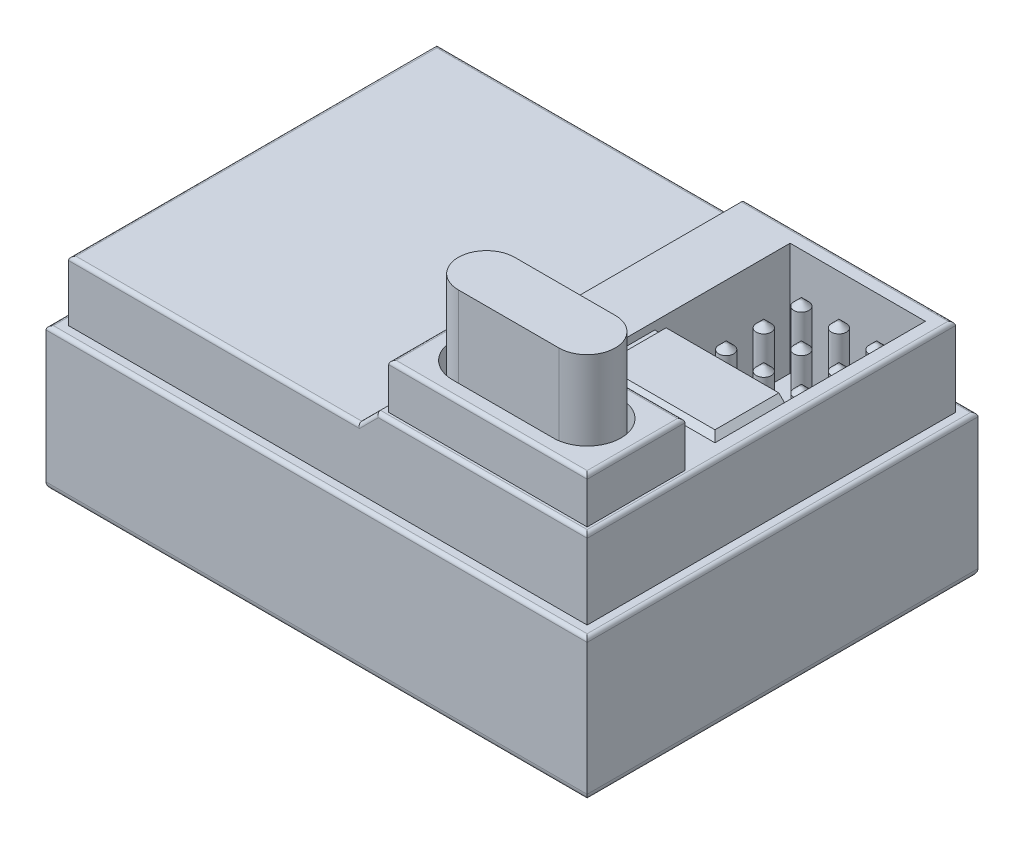
SolidWorks part; units mm, degrees
material "ABS"
ref_plane "Front Plane" through (0, 0, 0) normal (0, 0, 1) x (1, 0, 0)
ref_plane "Top Plane" through (0, 0, 0) normal (0, 1, 0) x (1, 0, 0)
ref_plane "Right Plane" through (0, 0, 0) normal (1, 0, 0) x (0, 0, -1)
sketch "Sketch1" plane through (0, 0, 0) normal (0, 1, 0) x (1, 0, 0)
  line L1 (-18, -13) -> (18, -13)
  line L2 (-18, -13) -> (-18, 13)
  line L3 (-18, 13) -> (18, 13)
  line L4 (18, -13) -> (18, 13)
  line L5 (-18, -13) -> (18, 13) construction
  line L6 (-18, 13) -> (18, -13) construction
  point P0 (0, 0)
  dimension "D1" = 26
  dimension "D2" = 36
extrude "Boss-Extrude1" add sketch "Sketch1" along normal blind 9.5
sketch "Sketch2" plane through (0, 9.5, 0) normal (0, 1, 0) x (1, 0, 0)
  line L0 (-18, 13) -> (-18, -13) construction
  line L1 (-17.25, -12.25) -> (17.25, -12.25)
  line L2 (-17.25, -12.25) -> (-17.25, 12.25)
  line L3 (-17.25, 12.25) -> (17.25, 12.25)
  line L4 (17.25, -12.25) -> (17.25, 12.25)
  line L5 (-17.25, -12.25) -> (17.25, 12.25) construction
  line L6 (-17.25, 12.25) -> (17.25, -12.25) construction
  line L7 (-18, -13) -> (18, -13) construction
  point P0 (0, 0)
  dimension "D1" = 0.75
  dimension "D2" = 0.75
extrude "Boss-Extrude2" add sketch "Sketch2" along normal blind 4
sketch "Sketch3" plane through (0, 13.5, 0) normal (0, 1, 0) x (1, 0, 0)
  line L0 (17.25, 12.25) -> (-17.25, 12.25) construction
  line L1 (17.25, -12.25) -> (2, -12.25)
  line L2 (17.25, -12.25) -> (17.25, 12.25)
  line L3 (17.25, 12.25) -> (2, 12.25)
  line L4 (2, -12.25) -> (2, 12.25)
  dimension "D1" = 15.25
extrude "Boss-Extrude3" add sketch "Sketch3" along normal blind 1.25
chamfer "Chamfer1" distance 1.25 angle 45 1 edges at (2, 14.75, 0)
sketch "Sketch4" plane through (0, 14.75, 0) normal (0, 1, 0) x (1, 0, 0)
  line L0 (3.25, -12.25) -> (17.25, -12.25) construction
  line L1 (16.85, -11.85) -> (3.65, -11.85)
  line L2 (16.85, -11.85) -> (16.85, -5.35)
  line L3 (16.85, -5.35) -> (3.65, -5.35)
  line L4 (3.65, -11.85) -> (3.65, -5.35)
  line L5 (17.25, -12.25) -> (17.25, 12.25) construction
  line L6 (3.25, 12.25) -> (3.25, -12.25) construction
  line L7 (6.9, -6.35) -> (13.6, -6.35)
  line L8 (13.6, -10.85) -> (6.9, -10.85)
  arc A0 (13.6, -6.35) -> (13.6, -10.85) centre (13.6, -8.6) cw
  arc A1 (6.9, -10.85) -> (6.9, -6.35) centre (6.9, -8.6) cw
  dimension "D7" = 1
  dimension "D8" = 1
  dimension "D1" = 0.4
  dimension "D2" = 0.4
  dimension "D3" = 0.4
  dimension "D4" = 6.5
  dimension "D5" = 1
  dimension "D6" = 1
extrude "Boss-Extrude4" add sketch "Sketch4" along normal blind 3
sketch "Sketch5" plane through (0, 14.75, 0) normal (0, 1, 0) x (1, 0, 0)
  line L0 (6.905, -6.725) -> (13.595, -6.725)
  line L1 (13.595, -10.475) -> (6.905, -10.475)
  line L2 (13.595, -8.6) -> (6.905, -8.6) construction
  line L3 (13.6, -6.35) -> (6.9, -6.35) construction
  line L4 (6.9, -10.85) -> (13.6, -10.85) construction
  line L5 (10.25, -10.85) -> (10.25, -6.35) construction
  line L6 (6.9, -10.85) -> (13.6, -10.85) construction
  arc A0 (13.595, -6.725) -> (13.595, -10.475) centre (13.595, -8.6) cw
  arc A1 (6.905, -10.475) -> (6.905, -6.725) centre (6.905, -8.6) cw
  arc A2 (6.9, -6.35) -> (6.9, -10.85) centre (6.9, -8.6) ccw construction
  point P5 (10.25, -6.35)
  point P7 (10.25, -10.85)
  point P16 (10.25, -8.6)
  point P17 (4.65, -8.6)
  dimension "D2" = 0.38
  dimension "D1" = 3.75
extrude "Boss-Extrude5" add sketch "Sketch5" along normal blind 8
sketch "Sketch6" plane through (0, 14.75, 0) normal (0, 1, 0) x (1, 0, 0)
  line L0 (17.25, 12.25) -> (3.25, 12.25) construction
  line L1 (7.25, 11.25) -> (16.25, 11.25)
  line L2 (7.25, 11.25) -> (7.25, -2.75)
  line L3 (7.25, -2.75) -> (16.25, -2.75)
  line L4 (16.25, 11.25) -> (16.25, -2.75)
  line L5 (17.25, -12.25) -> (17.25, 12.25) construction
  dimension "D1" = 14
  dimension "D2" = 1
  dimension "D3" = 1
  dimension "D4" = 9
extrude "Cut-Extrude1" cut sketch "Sketch6" against normal blind 7.5
sketch "Sketch7" plane through (0, 7.25, 0) normal (0, 1, 0) x (1, 0, 0)
  line L0 (16.25, 10) -> (7.25, 10) construction
  line L1 (16.25, -2.75) -> (16.25, 11.25) construction
  line L2 (7.25, 11.25) -> (7.25, -2.75) construction
  line L3 (16.25, 7.5) -> (7.25, 7.5) construction
  line L4 (7.25, 11.25) -> (7.25, -2.75) construction
  line L5 (7.25, 5) -> (16.25, 5) construction
  line L6 (16.25, 11.25) -> (7.25, 11.25) construction
  line L7 (14.25, 5) -> (14.25, 10) construction
  line L8 (9.25, 10) -> (9.25, 5) construction
  circle A0 centre (9.25, 10) radius 0.5
  circle A1 centre (11.75, 10) radius 0.5
  circle A2 centre (14.25, 10) radius 0.5
  circle A3 centre (9.25, 7.5) radius 0.5
  circle A4 centre (11.75, 7.5) radius 0.5
  circle A5 centre (14.25, 7.5) radius 0.5
  circle A6 centre (9.25, 5) radius 0.5
  circle A7 centre (11.75, 5) radius 0.5
  circle A8 centre (14.25, 5) radius 0.5
  point P14 (11.75, 10)
  point P15 (11.75, 7.5)
  point P16 (11.75, 5)
  dimension "D6" = 1
  dimension "D1" = 1.25
  dimension "D2" = 2.5
  dimension "D3" = 2.5
  dimension "D4" = 2.5
  dimension "D5" = 2.5
extrude "Boss-Extrude6" add sketch "Sketch7" along normal blind 6
chamfer "Chamfer3" distance 0.5 angle 45 9 edges at (14.25, 13.25, -4.5) (11.75, 13.25, -9.5) (11.75, 13.25, -4.5) (9.25, 13.25, -4.5) (9.25, 13.25, -7) (11.75, 13.25, -7) (14.25, 13.25, -7) (14.25, 13.25, -9.5) (9.25, 13.25, -9.5)
sketch "Sketch8" plane through (0, 7.25, 0) normal (0, 1, 0) x (1, 0, 0)
  line L0 (7.25, 11.25) -> (7.25, -2.75) construction
  line L1 (16.25, -2.75) -> (7.25, -2.75)
  line L2 (16.25, -2.75) -> (16.25, 2.25)
  line L3 (16.25, 2.25) -> (7.25, 2.25)
  line L4 (7.25, -2.75) -> (7.25, 2.25)
  dimension "D1" = 5
extrude "Boss-Extrude7" add sketch "Sketch8" along normal blind 7
sketch "Sketch9" plane through (0, 14.25, 0) normal (0, 1, 0) x (1, 0, 0)
  line L0 (16.25, 2.25) -> (7.25, 2.25) construction
  line L1 (8.25, 2.25) -> (15.25, 2.25)
  line L2 (8.25, 2.25) -> (8.25, -1.75)
  line L3 (8.25, -1.75) -> (15.25, -1.75)
  line L4 (15.25, 2.25) -> (15.25, -1.75)
  line L5 (16.25, -2.75) -> (16.25, 2.25) construction
  line L6 (7.25, -2.75) -> (16.25, -2.75) construction
  line L7 (7.25, 2.25) -> (7.25, -2.75) construction
  dimension "D1" = 1
  dimension "D2" = 1
  dimension "D3" = 1
extrude "Boss-Extrude8" add sketch "Sketch9" along normal blind 0.5
chamfer "Chamfer2" distance 0.75 angle 45 3 edges at (8.25, 14.25, -0.25) (11.75, 14.25, 1.75) (15.25, 14.25, -0.25)
fillet "Fillet1" radius 0.25 16 edges at (-18, 9.5, 0) (0, 9.5, 13) (18, 9.5, 0) (0, 9.5, -13) (10.25, 14.75, -12.25) (-17.25, 13.5, 0) (10.25, 14.75, 12.25) (17.25, 14.75, 0) (10.25, 17.75, 5.35) (3.65, 17.75, 8.6) (10.25, 17.75, 11.85) (16.85, 17.75, 8.6)
fillet "Fillet2" radius 0.5 4 edges at (18, 0, 0) (0, 0, -13) (-18, 0, 0) (0, 0, 13)
sketch "Sketch10" plane through (-18, 0, 0) normal (-1, 0, 0) x (0, 0, 1)
  line L1 (13, 9.25) -> (-13, 9.25) construction
  line L2 (13, 9.25) -> (13, 0.5) construction
  circle A0 centre (2, 4.25) radius 2
  circle A1 centre (2, 4.25) radius 1.5
  dimension "D2" = 3
  dimension "D3" = 4
  dimension "D1" = 11
  dimension "D4" = 5
extrude "Boss-Extrude9" add sketch "Sketch10" along normal blind 1
